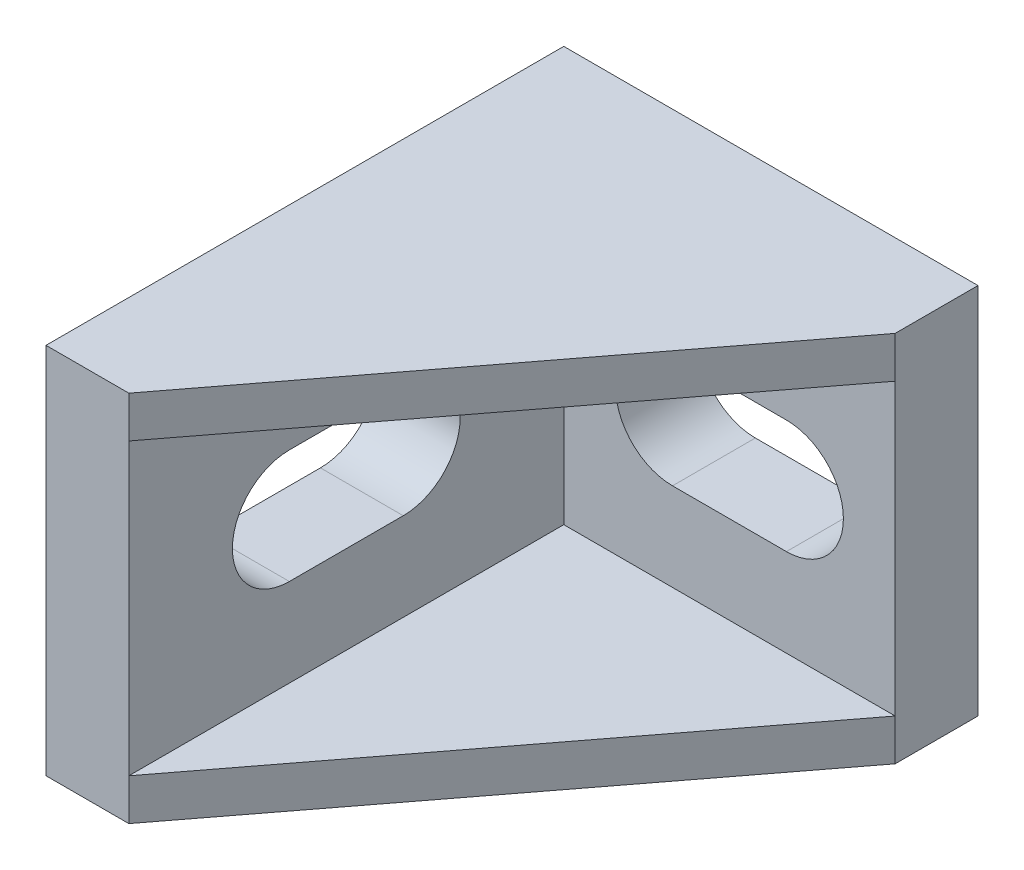
SolidWorks part; units mm, degrees
ref_plane "정면" through (0, 0, 0) normal (0, 0, 1) x (1, 0, 0)
ref_plane "윗면" through (0, 0, 0) normal (0, 1, 0) x (1, 0, 0)
ref_plane "우측면" through (0, 0, 0) normal (1, 0, 0) x (0, 0, -1)
sketch "스케치1" plane through (0, 0, 0) normal (0, 0, 1) x (1, 0, 0)
  line L1 (-10, 9) -> (10, 9)
  line L2 (-10, 9) -> (-10, -9)
  line L3 (-10, -9) -> (10, -9)
  line L4 (10, 9) -> (10, -9)
  line L5 (-10, 9) -> (10, -9) construction
  line L6 (-10, -9) -> (10, 9) construction
  point P0 (0, 0)
  dimension "D1" = 20
  dimension "D2" = 18
extrude "보스-돌출1" add sketch "스케치1" along normal blind 25
sketch "스케치2" plane through (0, 0, 25) normal (0, 0, 1) x (1, 0, 0)
  line L0 (10, -9) -> (10, 9) construction
  line L1 (10, 7) -> (-6, 7)
  line L2 (10, 7) -> (10, -7)
  line L3 (10, -7) -> (-6, -7)
  line L4 (-6, 7) -> (-6, -7)
  line L5 (-10, 9) -> (-10, -9) construction
  line L6 (10, 9) -> (-10, 9) construction
  line L7 (-10, -9) -> (10, -9) construction
  point P10 (0, 9)
  dimension "D1" = 4
  dimension "D2" = 2
  dimension "D3" = 2
extrude "컷-돌출1" cut sketch "스케치2" against normal blind 21
sketch "스케치4" plane through (0, -7, 0) normal (0, 1, 0) x (1, 0, 0)
  line L0 (-6, -25) -> (10, -4)
  line L1 (10, -4) -> (10, -25)
  line L2 (10, -25) -> (-6, -25)
extrude "컷-돌출2" cut sketch "스케치4" against normal through all both and the other way through all
sketch "스케치5" plane through (0, 0, 4) normal (0, 0, 1) x (1, 0, 0)
  line L0 (-0.75, 0) -> (4.75, 0) construction
  line L1 (-0.75, 2.75) -> (4.75, 2.75)
  line L2 (-0.75, -2.75) -> (4.75, -2.75)
  line L3 (10, -7) -> (10, 7) construction
  arc A0 (-0.75, 2.75) -> (-0.75, -2.75) centre (-0.75, 0) ccw
  arc A1 (4.75, -2.75) -> (4.75, 2.75) centre (4.75, 0) ccw
  point P3 (2, 0)
  point P8 (0, 0)
  dimension "D2" = 2.75
  dimension "D1" = 5.5
  dimension "D3" = 8
extrude "컷-돌출3" cut sketch "스케치5" against normal through all both
sketch "스케치6" plane through (-6, 0, 0) normal (1, 0, 0) x (0, 0, -1)
  line L0 (-17.25, 0) -> (-11.75, 0) construction
  line L1 (-17.25, 2.75) -> (-11.75, 2.75)
  line L2 (-17.25, -2.75) -> (-11.75, -2.75)
  line L3 (-4, -7) -> (-25, -7) construction
  line L4 (-25, 7) -> (-25, -7) construction
  arc A0 (-17.25, 2.75) -> (-17.25, -2.75) centre (-17.25, 0) ccw
  arc A1 (-11.75, -2.75) -> (-11.75, 2.75) centre (-11.75, 0) ccw
  point P2 (-14.5, 0)
  dimension "D2" = 2.75
  dimension "D1" = 5.5
  dimension "D3" = 7
  dimension "D4" = 10.5
extrude "컷-돌출4" cut sketch "스케치6" against normal through all both
